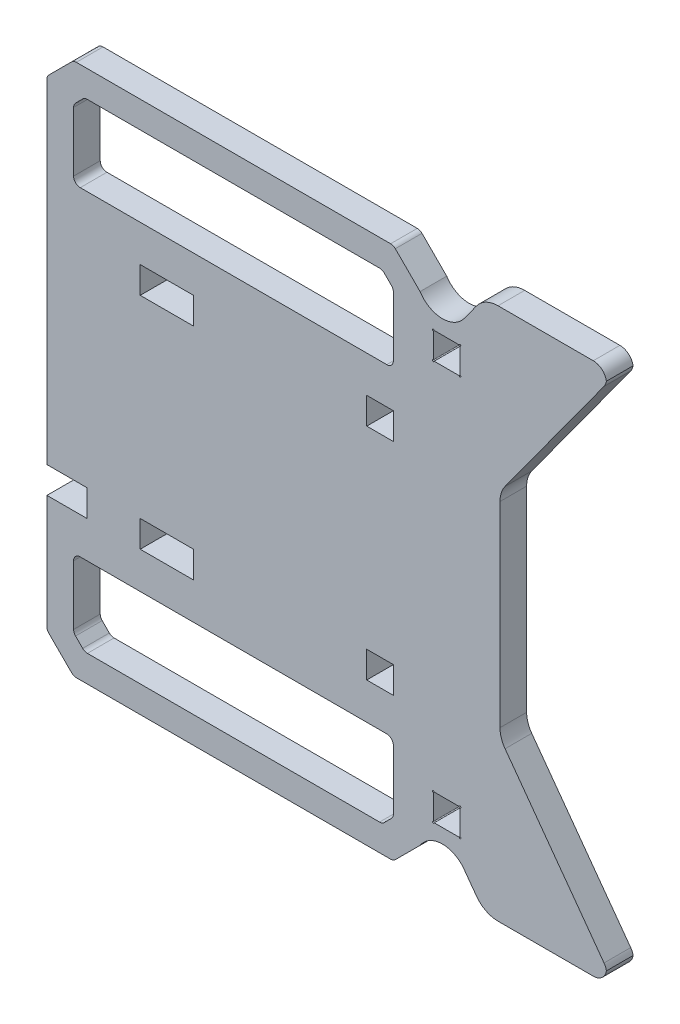
SolidWorks part; units mm, degrees
ref_plane "Front Plane" through (0, 0, 0) normal (0, 0, 1) x (1, 0, 0)
ref_plane "Top Plane" through (0, 0, 0) normal (0, 1, 0) x (1, 0, 0)
ref_plane "Right Plane" through (0, 0, 0) normal (1, 0, 0) x (0, 0, -1)
sketch "Sketch1" plane through (0, 0, 0) normal (0, 0, 1) x (1, 0, 0)
  line L0 (83.672, 0) -> (-43.8164, 0) construction
  line L1 (10.525, 38.1) -> (10.525, -38.1) construction
  line L2 (-27.575, 38.1) -> (48.625, 38.1)
  line L3 (99.425, -63.5) -> (99.425, -60.325)
  line L4 (99.425, -60.325) -> (74.025, -25.4)
  line L5 (-27.575, -63.5) -> (48.625, -63.5)
  line L6 (-27.575, 38.1) -> (-27.575, 54.5197)
  line L7 (48.625, 38.1) -> (48.625, 54.5197)
  line L8 (-24.9447, 57.15) -> (45.9947, 57.15)
  line L9 (-27.575, 63.5) -> (48.625, 63.5)
  line L10 (-33.925, 57.15) -> (-33.925, -57.15)
  line L11 (-27.575, 63.5) -> (-33.925, 57.15)
  line L12 (-24.9447, 57.15) -> (-27.575, 54.5197)
  line L13 (99.425, 63.5) -> (99.425, 60.325)
  line L14 (-23.0849, 59.0099) -> (-29.4349, 52.6599) construction
  line L15 (99.425, 60.325) -> (74.025, 25.4)
  line L16 (74.025, 25.4) -> (74.025, -25.4)
  line L17 (48.625, -38.1) -> (48.625, -54.5197)
  line L18 (-27.575, -38.1) -> (48.625, -38.1)
  line L19 (-24.9447, -57.15) -> (45.9947, -57.15)
  line L20 (-24.9447, -57.15) -> (-27.575, -54.5197)
  line L21 (-27.575, -38.1) -> (-27.575, -54.5197)
  line L22 (-27.575, -63.5) -> (-33.925, -57.15)
  line L23 (48.625, -63.5) -> (54.975, -57.15)
  line L24 (48.625, 63.5) -> (54.975, 57.15)
  line L25 (70.3271, -63.5) -> (99.425, -63.5)
  line L26 (45.9947, 57.15) -> (48.625, 54.5197)
  line L27 (45.9947, -57.15) -> (48.625, -54.5197)
  line L28 (70.3271, 63.5) -> (65.7089, 57.15)
  line L29 (70.3271, 63.5) -> (99.425, 63.5)
  line L30 (78.8831, 75.2646) -> (53.4831, 40.3396) construction
  line L31 (54.975, -42.3909) -> (54.975, -57.15)
  line L32 (70.3271, -63.5) -> (65.7089, -57.15)
  line L34 (48.625, -63.5) -> (54.975, -57.15)
  line L35 (65.7089, 57.15) -> (54.975, 42.3909)
  line L36 (54.975, 42.3909) -> (54.975, 57.15)
  line L37 (65.7089, -57.15) -> (54.975, -42.3909)
  point P7 (-27.575, 0)
  point P21 (74.025, 0)
  point P22 (-33.925, 0)
  dimension "D1" = 25.4
  dimension "D2" = 76.2
  dimension "D3" = 127
  dimension "D4" = 6.35
  dimension "D7" = 3.175
  dimension "D8" = 25.4
  dimension "D9" = 25.4
  dimension "D6" = 6.35
extrude "Boss-Extrude1" add sketch "Sketch1" along normal blind 6.35 contours L23 L32 L25 L3 L4 L16 L15 L13 L29 L28 L24 L9 L11 L10 L22 L5 L8 L26 L7 L2 L6 L12 L27 L19 L20 L21 L18 L17 region at (27.1557, 0, 0)
fillet "Fillet1" radius 6.35 4 edges at (70.3271, 63.5, 3.175) (70.3271, -63.5, 3.175) (54.975, -42.3909, 3.175) (54.975, 42.3909, 3.175)
fillet "Fillet3" radius 3.175 4 edges at (99.425, 63.5, 3.175) (99.425, 60.325, 3.175) (99.425, -60.325, 3.175) (99.425, -63.5, 3.175)
fillet "Fillet4" radius 6.35 2 edges at (74.025, -25.4, 3.175) (74.025, 25.4, 3.175)
fillet "Fillet7" radius 1.5875 4 edges at (-27.575, -38.1, 3.175) (48.625, -38.1, 3.175) (48.625, 38.1, 3.175) (-27.575, 38.1, 3.175)
fillet "Fillet8" radius 1.5875 6 edges at (-33.925, -57.15, 3.175) (-27.575, -63.5, 3.175) (48.625, -63.5, 3.175) (48.625, 63.5, 3.175) (-27.575, 63.5, 3.175) (-33.925, 57.15, 3.175)
fillet "Fillet9" radius 1.5875 8 edges at (-27.575, 54.5197, 3.175) (-24.9447, 57.15, 3.175) (-27.575, -54.5197, 3.175) (-24.9447, -57.15, 3.175) (45.9947, -57.15, 3.175) (48.625, -54.5197, 3.175) (48.625, 54.5197, 3.175) (45.9947, 57.15, 3.175)
sketch "Sketch2" plane through (0, 0, 6.35) normal (0, 0, 1) x (1, 0, 0)
  line L0 (-33.925, 0) -> (74.025, 0) construction
  line L1 (-33.925, 56.4924) -> (-33.925, -56.4924) construction
  line L2 (74.025, 23.3351) -> (74.025, -23.3351) construction
  line L3 (48.625, 39.6875) -> (48.625, 53.8622) construction
  line L4 (58.3484, 50.8) -> (64.3016, 50.8)
  line L5 (58.15, 50.6016) -> (58.15, 44.6484)
  line L6 (58.3484, 44.45) -> (64.3016, 44.45)
  line L7 (64.5, 50.6016) -> (64.5, 44.6484)
  line L8 (64.5, -50.6016) -> (64.5, -44.6484)
  line L9 (58.3484, -50.8) -> (64.3016, -50.8)
  line L10 (58.15, -50.6016) -> (58.15, -44.6484)
  line L11 (58.3484, -44.45) -> (64.3016, -44.45)
  arc A0 (58.3484, 50.8) -> (58.15, 50.6016) centre (58.15, 50.8) ccw
  arc A1 (64.5, 50.6016) -> (64.3016, 50.8) centre (64.5, 50.8) ccw
  arc A2 (64.3016, 44.45) -> (64.5, 44.6484) centre (64.5, 44.45) ccw
  arc A3 (58.15, 44.6484) -> (58.3484, 44.45) centre (58.15, 44.45) ccw
  arc A4 (64.3016, -44.45) -> (64.5, -44.6484) centre (64.5, -44.45) cw
  arc A5 (64.5, -50.6016) -> (64.3016, -50.8) centre (64.5, -50.8) cw
  arc A6 (58.3484, -50.8) -> (58.15, -50.6016) centre (58.15, -50.8) cw
  arc A7 (58.15, -44.6484) -> (58.3484, -44.45) centre (58.15, -44.45) cw
  point P10 (48.625, 46.7748)
  dimension "D5" = 0.3969
  dimension "D6" = 0.3969
  dimension "D7" = 0.3969
  dimension "D8" = 0.3969
  dimension "D1" = 6.35
  dimension "D2" = 6.35
  dimension "D3" = 50.8
  dimension "D4" = 9.525
extrude "Cut-Extrude1" cut sketch "Sketch2" against normal through all
sketch "Sketch3" plane through (0, 0, 6.35) normal (0, 0, 1) x (1, 0, 0)
  line L0 (1, 29.3687) -> (1, -29.3687) construction
  line L1 (44.8469, 29.3687) -> (44.8469, -29.3687) construction
  line L2 (48.4188, 29.3687) -> (41.275, 29.3687) construction
  line L3 (48.4187, -29.3687) -> (41.275, -29.3687) construction
  line L4 (44.8469, 0) -> (-40.6002, 0) construction
  line L5 (1, 29.3687) -> (-11.7, 29.3687)
  line L6 (1, -29.3687) -> (-11.7, -29.3687)
  line L7 (1, -29.3687) -> (1, -23.0187)
  line L8 (1, -23.0187) -> (-11.7, -23.0187)
  line L9 (-11.7, -29.3687) -> (-11.7, -23.0187)
  line L10 (42.275, -29.3687) -> (48.625, -29.3687)
  line L11 (42.275, -29.3687) -> (42.275, -23.0187)
  line L12 (42.275, -23.0187) -> (48.625, -23.0187)
  line L13 (48.625, -29.3687) -> (48.625, -23.0187)
  line L14 (1, 29.3687) -> (1, 23.0187)
  line L15 (-11.7, 29.3687) -> (-11.7, 23.0187)
  line L16 (1, 23.0187) -> (-11.7, 23.0187)
  line L17 (48.625, 29.3687) -> (48.625, 23.0187)
  line L18 (42.275, 29.3687) -> (48.625, 29.3687)
  line L19 (42.275, 29.3687) -> (42.275, 23.0187)
  line L20 (42.275, 23.0187) -> (48.625, 23.0187)
  line L21 (-33.925, 56.4924) -> (-33.925, -56.4924) construction
  line L22 (-33.925, -29.3687) -> (-24.4, -29.3687)
  line L23 (-33.925, -29.3687) -> (-33.925, -23.0187)
  line L24 (-33.925, -23.0187) -> (-24.4, -23.0187)
  line L25 (-24.4, -29.3687) -> (-24.4, -23.0187)
  line L26 (-24.4, -29.3687) -> (-33.925, -29.3687) construction
  dimension "D1" = 6.35
  dimension "D2" = 12.7
  dimension "D3" = 6.35
  dimension "D4" = 6.35
extrude "Cut-Extrude2" cut sketch "Sketch3" against normal through all
